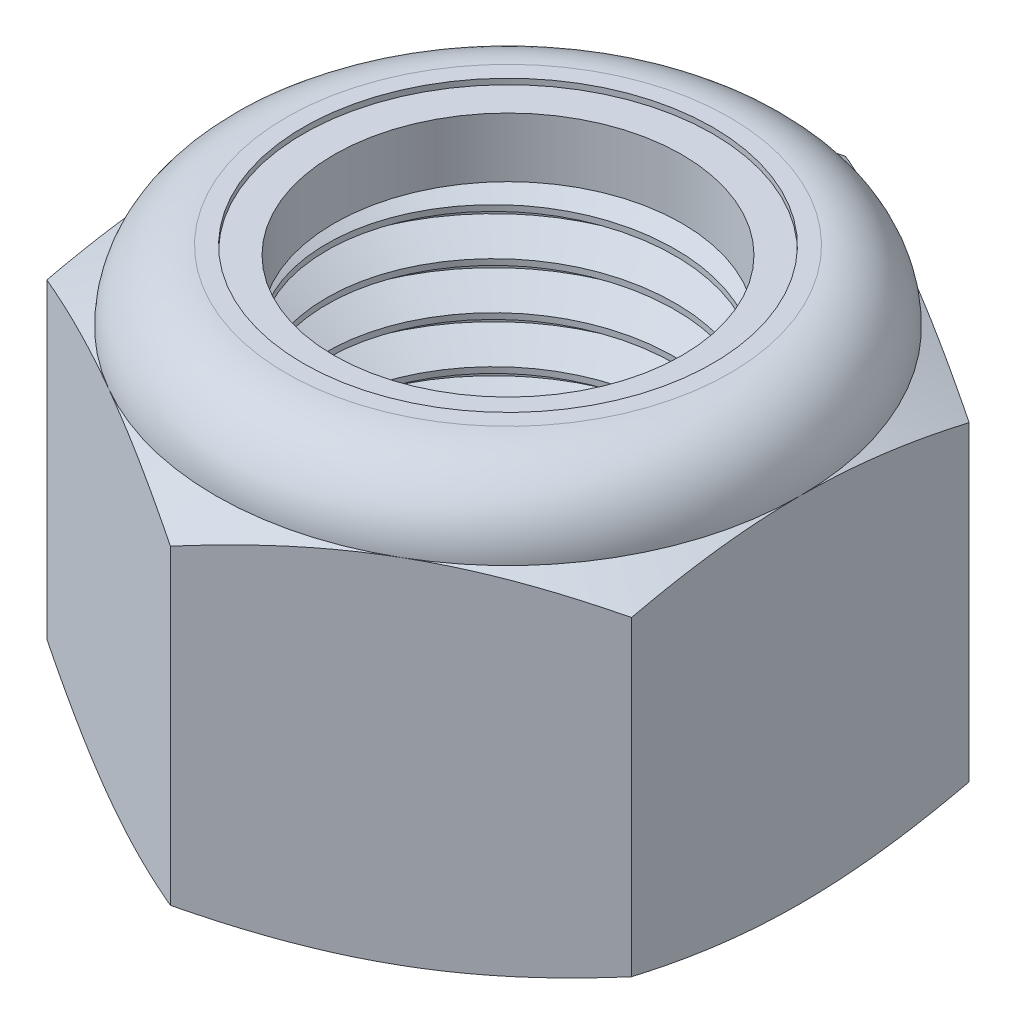
SolidWorks part; units mm, degrees
note: '?' marks a value the reader was unsure of.
ref_plane "Front" through (0, 0, 0) normal (0, 0, 1) x (1, 0, 0)
ref_plane "Top" through (0, 0, 0) normal (0, 1, 0) x (1, 0, 0)
ref_plane "Right" through (0, 0, 0) normal (1, 0, 0) x (0, 0, -1)
sketch "Sketch8" plane through (0, 0, 0) normal (1, 0, 0) x (0, 0, -1)
  line L0 (0, 0) -> (0, 11.5094) construction
  line L1 (7.9375, 0) -> (-7.9375, 0) construction
  line L2 (-5.5562, 11.5094) -> (5.5562, 11.5094) construction
  line L3 (5.5562, 11.5094) -> (5.5562, 10.2394) construction
sketch "Sketch1" plane through (0, 0, 0) normal (0, 1, 0) x (1, 0, 0)
  line L1 (0, 9.1654) -> (-7.9375, 4.5827)
  line L2 (-7.9375, 4.5827) -> (-7.9375, -4.5827)
  line L3 (-7.9375, -4.5827) -> (0, -9.1654)
  line L4 (0, -9.1654) -> (7.9375, -4.5827)
  line L5 (7.9375, -4.5827) -> (7.9375, 4.5827)
  line L6 (7.9375, 4.5827) -> (0, 9.1654)
  circle A0 centre (0, 0) radius 7.9375 construction
  circle A1 centre (0, 0) radius 5.5562
extrude "Extrude1" add sketch "Sketch1" along normal up to vertex (11.5094 mm away) up to point (0, 11.5094, 0)
sketch "Sketch5" plane through (0, 0, 0) normal (1, 0, 0) x (0, 0, -1)
  line L0 (0, 0) -> (7.9375, 0)
  line L1 (7.9375, 0) -> (9.1654, 0.5726)
  line L2 (9.1654, 0.5726) -> (9.1654, 9.0186)
  line L3 (9.1654, 9.0186) -> (7.9375, 9.5911)
  line L4 (6.0193, 11.5094) -> (6.0193, 12.7794)
  line L5 (6.0193, 12.7794) -> (10.4354, 12.7794)
  line L6 (10.4354, 12.7794) -> (10.4354, -1.27)
  line L7 (10.4354, -1.27) -> (0, -1.27)
  line L8 (0, -1.27) -> (0, 0)
  line L9 (7.9375, 9.5911) -> (7.9375, 0) construction
  line L12 (9.1654, 11.5094) -> (9.1654, 0) construction
  line L13 (9.1654, 5.7547) -> (10.4354, 5.7547) construction
  line L15 (0, 0) -> (0, 12.7794) construction
  line L18 (7.9375, 0) -> (-7.9375, 0) construction
  line L19 (4.5827, 11.5094) -> (9.1654, 11.5094) construction
  line L20 (0, 12.7794) -> (6.0193, 12.7794) construction
  line L21 (4.5827, 0) -> (9.1654, 0) construction
  arc A0 (7.9375, 9.5911) -> (6.0193, 11.5094) centre (6.0193, 9.5911) ccw
  dimension "D1" = 25
  dimension "D2" = 1.27
  dimension "D4" = 1.9182
revolve "Cut-Revolve3" cut sketch "Sketch5" angle 360 about L15
sketch "Sketch4" plane through (0, 0, 0) normal (1, 0, 0) x (0, 0, -1)
  line L0 (0, 9.5911) -> (6.1119, 9.5911)
  line L1 (6.1119, 9.5911) -> (0, 6.7411)
  line L3 (0, 2.85) -> (6.1119, 0)
  line L4 (6.1119, 0) -> (0, 0)
  line L5 (0, 0) -> (0, 9.5911) construction
  line L10 (0, 0) -> (0, 11.5094) construction
  line L11 (0, 2.85) -> (0, 0)
  line L12 (0, 9.5911) -> (0, 6.7411)
  line L13 (6.8741, 9.5911) -> (0, 9.5911) construction
  dimension "D1" = 25
  dimension "D2" = 12.2237
sketch "Sketch6" plane through (0, 0, 0) normal (1, 0, 0) x (0, 0, -1)
  line L0 (0, 9.5911) -> (7.7851, 9.5911)
  line L1 (6.0193, 11.357) -> (3.0096, 11.357)
  line L2 (0, 12.7794) -> (0, 9.5911)
  line L3 (3.0096, 12.7794) -> (0, 12.7794)
  line L4 (0, 12.7794) -> (6.0193, 12.7794) construction
  line L5 (0, 0) -> (0, 12.7794) construction
  line L6 (0, 12.7794) -> (0, 0) construction
  line L7 (3.0096, 11.357) -> (3.0096, 12.7794)
  line L8 (6.0193, 11.5094) -> (6.0193, 11.357) construction
  line L9 (3.0096, 11.357) -> (0, 11.357) construction
  line L10 (0, 11.357) -> (0, 6.7411) construction
  arc A0 (7.7851, 9.5911) -> (6.0193, 11.357) centre (6.0193, 9.5911) ccw
  arc A1 (7.9375, 9.5911) -> (6.0193, 11.5094) centre (6.0193, 9.5911) ccw construction
  dimension "D1" = 0.1524
revolve "Cut-Revolve4" cut sketch "Sketch6" angle 360 about L6
revolve "Cut-Revolve2" cut sketch "Sketch4" angle 360 about L5
sketch "Sketch7" plane through (0, 0, 0) normal (1, 0, 0) x (0, 0, -1)
  line L0 (4.7228, 9.6673) -> (7.7072, 9.6673)
  line L1 (6.0193, 11.2808) -> (4.7228, 11.2808)
  line L2 (4.7228, 11.2808) -> (4.7228, 9.6673)
  line L3 (4.7228, 9.6673) -> (0, 9.6673) construction
  line L4 (0, 9.6673) -> (0, 11.2808) construction
  line L5 (0, 11.2808) -> (4.7228, 11.2808) construction
  line L6 (4.7228, 9.6673) -> (4.7228, 9.5911) construction
  line L7 (0, 9.5911) -> (7.7851, 9.5911) construction
  line L8 (6.0193, 11.2808) -> (6.0193, 11.357) construction
  arc A0 (7.7072, 9.6673) -> (6.0193, 11.2808) centre (6.0193, 9.5911) ccw
  arc A2 (7.7851, 9.5911) -> (6.0193, 11.357) centre (6.0193, 9.5911) ccw construction
  dimension "D1" = 0.0762
  dimension "D2" = 9.4456
revolve "Revolve2" add sketch "Sketch7" angle 360 about L4
sketch "Sketch2" plane through (0, 0, 0) normal (1, 0, 0) x (0, 0, -1)
  line L0 (-5.5562, 0) -> (-5.5562, 9.5911) construction
  line L1 (0, 0) -> (5.5562, 0)
  line L2 (0, 0) -> (0, 9.5911)
  line L3 (0, 9.5911) -> (5.5562, 9.5911)
  line L4 (5.5562, 0) -> (5.5562, 9.5911)
  line L6 (6.8741, 9.5911) -> (7.9375, 9.5911) construction
  line L7 (0, -5.5562) -> (0, 0) construction
revolve "Revolve1" add sketch "Sketch2" angle 360 about L7
sketch "Sketch9" plane through (0, 0, 0) normal (1, 0, 0) x (0, 0, -1)
  line L0 (5.6937, 10.7818) -> (5.6937, 9.5118) construction
  line L1 (5.6937, 9.5118) -> (4.5939, 10.1468) construction
  line L2 (4.5939, 10.1468) -> (5.6937, 10.7818) construction
  line L3 (4.7314, 10.2261) -> (4.7314, 10.0674) construction
  line L4 (5.5562, 10.7024) -> (5.5562, 9.5911) construction
  line L5 (4.5939, 10.1468) -> (4.7314, 10.1468) construction
  line L6 (5.5563, 10.1468) -> (5.6937, 10.1468) construction
  line L7 (5.625, 10.1468) -> (5.625, 10.7421) construction
  line L8 (5.6937, 9.5118) -> (5.625, 10.7421)
  line L9 (5.625, 10.7421) -> (4.7314, 10.2261)
  line L10 (4.7314, 10.2261) -> (4.7314, 10.0674)
  line L11 (4.7314, 10.0674) -> (5.6937, 9.5118)
  dimension "D1" = 1.27
  dimension "D2" = 0.1588
sketch "Sketch10" plane through (0, 9.5911, 0) normal (0, 1, 0) x (1, 0, 0)
  circle A1 centre (0, 0) radius 5.5562
  circle A2 centre (0, 0) radius 5.5562
  dimension "D1" = 0
curve "Helix/Spiral1" pitch 1.27 height 12.7794 turns 10.0625
sweep "Cut-Sweep1" cut profiles "Sketch9" path "Helix/Spiral1" align with end faces yes
sketch "Sketch11" plane through (0, 0, 0) normal (1, 0, 0) x (0, 0, -1)
  line L0 (0, 0) -> (0, 11.5094) construction
  line L1 (7.9375, 0) -> (-7.9375, 0) construction
  line L4 (0, 11.5094) -> (0, 0) construction
  line L5 (0, 5.7547) -> (5.5563, 5.7547) construction
  line L6 (0, 0) -> (6.1119, 0)
  line L7 (0, 2.85) -> (0, 0)
  line L8 (6.1119, 0) -> (0, 2.85)
  dimension "D1" = 12.2237
  dimension "D2" = 25
revolve "Revolve3" add sketch "Sketch11" angle 360 about L4
sketch "Sketch12" plane through (0, 0, 0) normal (1, 0, 0) x (0, 0, -1)
  line L0 (6.1119, 9.5911) -> (0, 9.5911)
  line L1 (0, 9.5911) -> (0, 0)
  line L2 (0, 0) -> (6.1119, 0)
  line L3 (7.9375, 0) -> (-7.9375, 0) construction
  line L4 (6.1119, 0) -> (6.1119, 9.5911)
  line L5 (-6.1119, 0) -> (6.1119, 0) construction
revolve "Revolve4" add sketch "Sketch12" angle 360 about L0
combine bodies "Combine1" operation type subtract main body 136 bodies to subtract 133
ref_plane "Contact Plane 1" through (0, 0, 0) normal (0, -1, 0) x (1, 0, 0)
ref_axis "Center Axis 1" through (0, -2.1015, 0) along (0, 1, 0)?
equation "\"D4@Sketch5\"=\"Height@Sketch8\"/6"
equation "\"D1@Sketch9\"=\"Thread Pitch@Sketch8\""
equation "\"D2@Sketch9\"=\"Thread Pitch@Sketch8\"/8"
equation "\"D4@Helix/Spiral1\"=\"Thread Pitch@Sketch8\""
equation "\"D3@Helix/Spiral1\"=\"Thread Pitch@Sketch8\"+\"Height@Sketch8\""
equation "\"D2@Sketch4\"=\"Thread Dia@Sketch8\"*1.1"
equation "\"D1@Sketch11\"=\"Thread Dia@Sketch8\"*1.1"
equation "\"D2@Sketch7\"=\"Thread Dia@Sketch8\"*.85"
